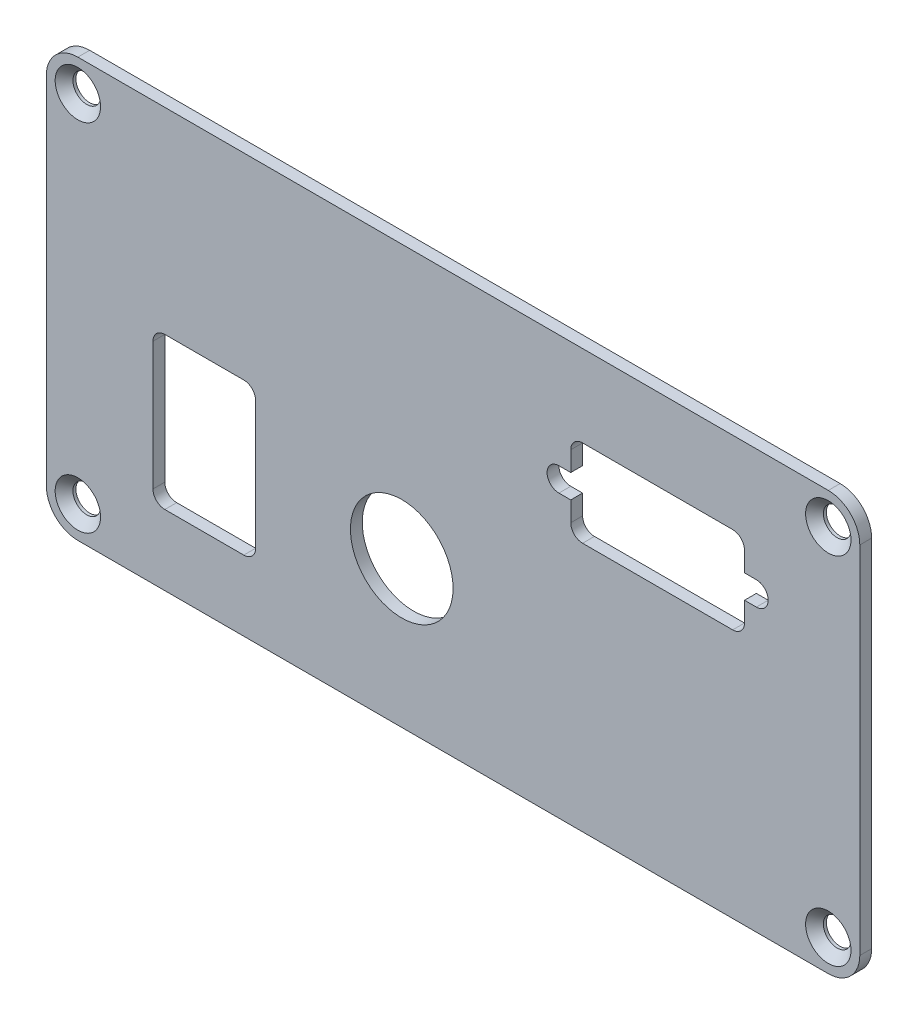
SolidWorks part; units mm, degrees
ref_plane "Plan de face" through (0, 0, 0) normal (0, 0, 1) x (1, 0, 0)
ref_plane "Plan de dessus" through (0, 0, 0) normal (0, 1, 0) x (1, 0, 0)
ref_plane "Plan de droite" through (0, 0, 0) normal (1, 0, 0) x (0, 0, -1)
ref_plane "Plan1" through (0, 0, -0.75) normal (0, 0, -1) x (-1, 0, 0)
sketch "Esquisse1" plane through (0, 0, -0.75) normal (0, 0, -1) x (-1, 0, 0)
  line L0 (-51.5, -26.5) -> (51.5, -26.5)
  line L1 (51.5, -26.5) -> (51.5, 26.5)
  line L2 (51.5, 26.5) -> (-51.5, 26.5)
  line L3 (-51.5, 26.5) -> (-51.5, -26.5)
extrude "Boss.-Extru.1" add sketch "Esquisse1" against normal blind 1.5
hole_wizard "Fraisage pour vis à tête fraisée M31" positions "Esquisse3" profile "Esquisse2" countersink size "M3" standard "Ansi Metric"
sketch "Esquisse3" plane through (0, 0, 0.75) normal (0, 0, 1) x (1, 0, 0)
  point P0 (-47.51, 22.5)
  point P1 (47.51, 22.5)
  point P2 (47.51, -22.5)
  point P3 (-47.51, -22.5)
sketch "Esquisse2" plane through (-47.51, 22.5, 0.75) normal (1, 0, 0) x (0, -1, 0)
  line L0 (0, 0) -> (0, 1.5)
  line L1 (0, 1.5) -> (1.75, 1.5)
  line L2 (1.75, 1.5) -> (1.75, 1.125)
  line L3 (1.75, 1.125) -> (2.875, 0)
  line L5 (2.875, 0) -> (0, 0)
  line L6 (-1.75, 1.125) -> (-2.875, 0) construction
  line L11 (0, -6.35) -> (0, 107.95) construction
  dimension "Diamètre du perçage jusqu'au prochain" = 3.5
  dimension "Profondeur du perçage jusqu'au prochain" = 1.5
  dimension "Diamètre du fraisage entrant" = 5.75
  dimension "Angle du fraisage entrant" = 90
fillet "Congé1" radius 3.99 4 edges at (51.5, 26.5, 0) (51.5, -26.5, 0) (-51.5, 26.5, 0) (-51.5, -26.5, 0) tangent propagation no
sketch "Esquisse5" plane through (0, 0, 0.75) normal (0, 0, 1) x (1, 0, 0)
  line L0 (-51.5, 0) -> (51.5, 0) construction
  line L1 (-51.5, -22.51) -> (-51.5, 22.51) construction
  line L2 (51.5, 22.51) -> (51.5, -22.51) construction
  line L3 (0, 26.5) -> (0, -26.5) construction
  line L4 (-47.51, 26.5) -> (47.51, 26.5) construction
  line L5 (47.51, -26.5) -> (-47.51, -26.5) construction
  line L6 (25.9, 16.15) -> (25.9, 5.15) construction
  line L7 (-26.5, -17.6) -> (-36.5, -17.6)
  line L8 (-25, -16.1) -> (-25, 0.1)
  line L9 (-26.5, 1.6) -> (-36.5, 1.6)
  line L10 (-38, -16.1) -> (-38, 0.1)
  line L11 (-25, -17.6) -> (-38, 1.6) construction
  line L12 (-25, 1.6) -> (-38, -17.6) construction
  line L13 (35.4, 5.15) -> (16.4, 5.15)
  line L14 (36.9, 6.65) -> (36.9, 9.15)
  line L15 (35.4, 16.15) -> (16.4, 16.15)
  line L16 (14.9, 6.65) -> (14.9, 9.15)
  line L17 (36.9, 5.15) -> (14.9, 16.15) construction
  line L18 (36.9, 16.15) -> (14.9, 5.15) construction
  line L19 (38.4, 12.15) -> (36.9, 12.15)
  line L20 (38.4, 9.15) -> (36.9, 9.15)
  line L21 (36.9, 12.15) -> (36.9, 14.65)
  line L22 (13.4, 9.15) -> (14.9, 9.15)
  line L23 (13.4, 12.15) -> (14.9, 12.15)
  line L24 (14.9, 12.15) -> (14.9, 14.65)
  arc A0 (38.4, 9.15) -> (38.4, 12.15) centre (38.4, 10.65) ccw
  arc A1 (13.4, 9.15) -> (13.4, 12.15) centre (13.4, 10.65) cw
  circle A2 centre (-6.5, -8) radius 6.5
  arc A3 (-25, 0.1) -> (-26.5, 1.6) centre (-26.5, 0.1) ccw
  arc A4 (-36.5, 1.6) -> (-38, 0.1) centre (-36.5, 0.1) ccw
  arc A5 (-38, -16.1) -> (-36.5, -17.6) centre (-36.5, -16.1) ccw
  arc A6 (-26.5, -17.6) -> (-25, -16.1) centre (-26.5, -16.1) ccw
  arc A7 (36.9, 6.65) -> (35.4, 5.15) centre (35.4, 6.65) cw
  arc A8 (16.4, 5.15) -> (14.9, 6.65) centre (16.4, 6.65) cw
  arc A9 (14.9, 14.65) -> (16.4, 16.15) centre (16.4, 14.65) cw
  arc A10 (36.9, 14.65) -> (35.4, 16.15) centre (35.4, 14.65) ccw
  point P12 (-31.5, -8)
  point P17 (25.9, 10.65)
  dimension "D9" = 25
  dimension "D10" = 1.5
  dimension "D11" = 13
  dimension "D14" = 1.5
  dimension "D2" = 8
  dimension "D3" = 19.2
  dimension "D4" = 13
  dimension "D5" = 25.6
  dimension "D6" = 22
  dimension "D7" = 11
  dimension "D8" = 15.85
  dimension "D12" = 25
  dimension "D13" = 20
extrude "Enlèv. mat.-Extru.1" cut sketch "Esquisse5" against normal through all
